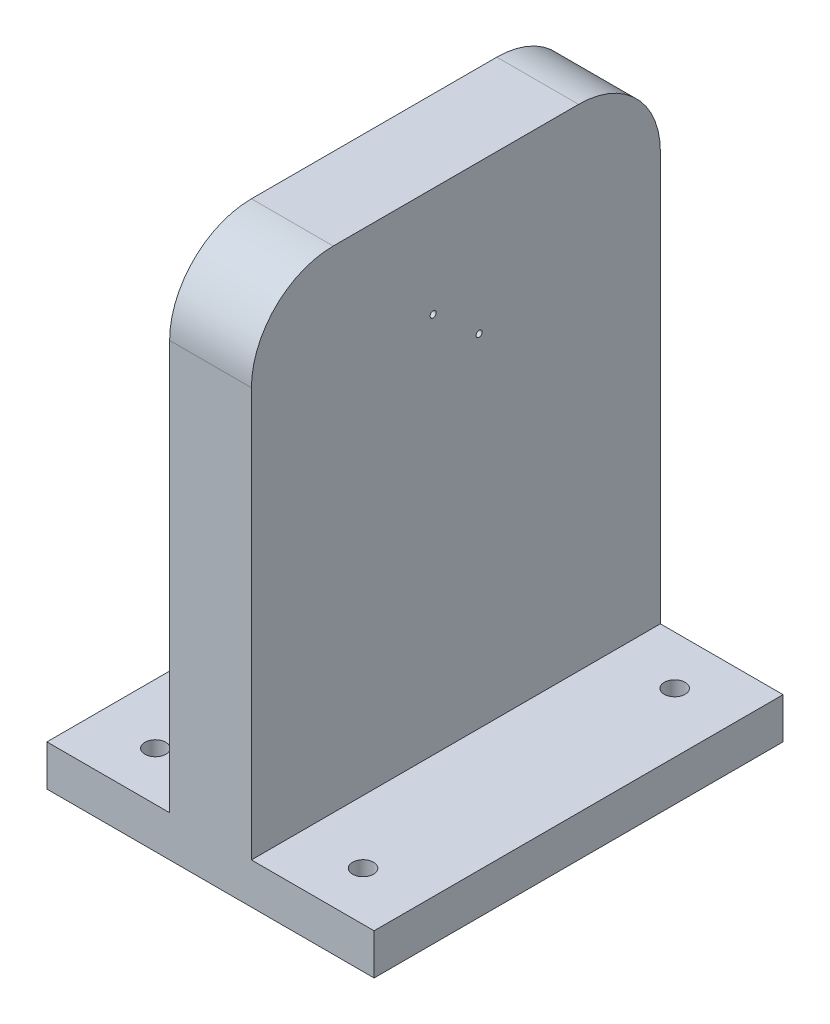
SolidWorks part; units mm, degrees
ref_plane "Front Plane" through (0, 0, 0) normal (0, 0, 1) x (1, 0, 0)
ref_plane "Top Plane" through (0, 0, 0) normal (0, 1, 0) x (1, 0, 0)
ref_plane "Right Plane" through (0, 0, 0) normal (1, 0, 0) x (0, 0, -1)
sketch "Sketch2" plane through (0, 0, 0) normal (0, 1, 0) x (1, 0, 0)
  line L1 (-40, -50) -> (40, -50)
  line L2 (-40, -50) -> (-40, 50)
  line L3 (-40, 50) -> (40, 50)
  line L4 (40, -50) -> (40, 50)
  line L5 (-40, -50) -> (40, 50) construction
  line L6 (-40, 50) -> (40, -50) construction
  point P0 (0, 0)
  dimension "D1" = 100
  dimension "D2" = 80
extrude "Boss-Extrude1" add sketch "Sketch2" along normal blind 10 contours L2 L3 L4 L1
sketch "Sketch3" plane through (0, 10, 0) normal (0, 1, 0) x (1, 0, 0)
  line L0 (-40, 50) -> (40, 50) construction
  line L1 (-10, -50) -> (10, -50)
  line L2 (-10, -50) -> (-10, 50)
  line L3 (-10, 50) -> (10, 50)
  line L4 (10, -50) -> (10, 50)
  line L5 (-10, -50) -> (10, 50) construction
  line L6 (-10, 50) -> (10, -50) construction
  point P0 (0, 0)
  dimension "D1" = 20
extrude "Boss-Extrude2" add sketch "Sketch3" along normal blind 120
sketch "Sketch4" plane through (-10, 0, 0) normal (-1, 0, 0) x (0, 0, 1)
  line L0 (0, 130) -> (0, 0) construction
  line L1 (-50, 130) -> (50, 130) construction
  line L2 (-50, 98.5) -> (50, 98.5) construction
  line L3 (-50, 130) -> (-50, 10) construction
  line L4 (50, 130) -> (50, 10) construction
  line L5 (50, 0) -> (-50, 0) construction
  line L7 (-12.5, 87.7) -> (12.5, 87.7) construction
  line L8 (-12.5, 87.7) -> (-12.5, 109.3) construction
  line L9 (-12.5, 109.3) -> (12.5, 109.3) construction
  line L10 (12.5, 87.7) -> (12.5, 109.3) construction
  line L11 (-12.5, 87.7) -> (12.5, 109.3) construction
  line L12 (-12.5, 109.3) -> (12.5, 87.7) construction
  circle A0 centre (-5.6862, 93.5871) radius 0.75
  circle A1 centre (5.5657, 103.3088) radius 0.75
  point P13 (0, 98.5)
  dimension "D6" = 1.5
  dimension "D7" = 1.5
  dimension "D1" = 98.5
  dimension "D2" = 25
  dimension "D3" = 21.6
  dimension "D4" = 14.87
  dimension "D5" = 7.435
extrude "Cut-Extrude1" cut sketch "Sketch4" against normal blind 55 contours A0 | A1
sketch "Sketch5" plane through (0, 0, 0) normal (0, -1, 0) x (1, 0, 0)
  line L0 (0, 50) -> (0, -50) construction
  line L1 (-40, 50) -> (40, 50) construction
  line L2 (-40, -50) -> (40, -50) construction
  line L3 (-40, 0) -> (40, 0) construction
  line L4 (-40, 50) -> (-40, -50) construction
  line L5 (40, 50) -> (40, -50) construction
  line L6 (-40, 38.1) -> (40, 38.1) construction
  line L7 (-40, -38.1) -> (40, -38.1) construction
  line L8 (-25.4, 50) -> (-25.4, -50) construction
  line L9 (25.4, 50) -> (25.4, -50) construction
  circle A0 centre (-25.4, -38.1) radius 2.555
  circle A1 centre (25.4, -38.1) radius 2.555
  circle A2 centre (-25.4, 38.1) radius 2.555
  circle A3 centre (25.4, 38.1) radius 2.555
  point P22 (0, 0)
  dimension "D5" = 5.11
  dimension "D1" = 76.2
  dimension "D2" = 38.1
  dimension "D3" = 50.8
  dimension "D4" = 25.4
extrude "Cut-Extrude2" cut sketch "Sketch5" against normal blind 55 contours A2 | A0 | A1 | A3
fillet "Fillet2" radius 20 2 edges at (0, 130, -50) (0, 130, 50)
